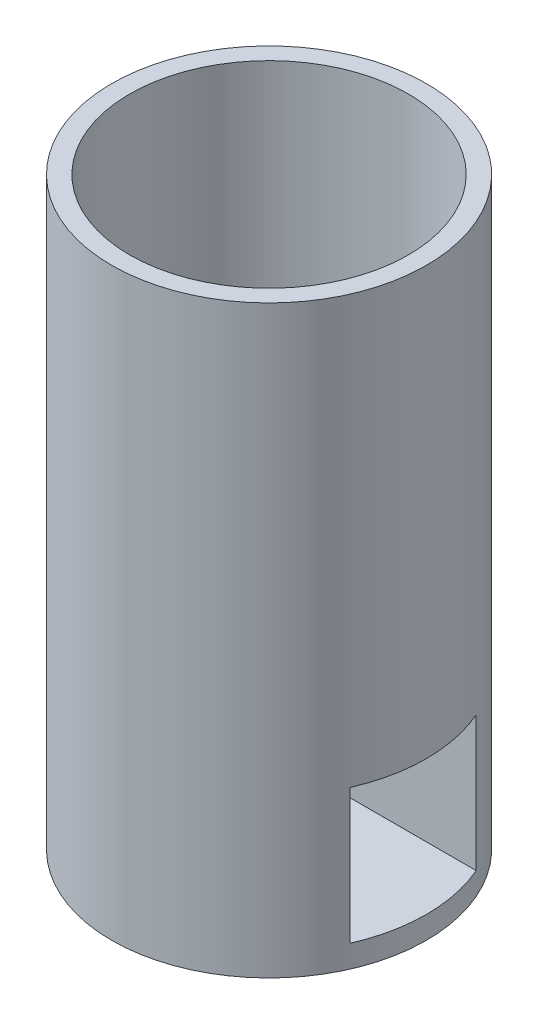
SolidWorks part; units mm, degrees
ref_plane "Front Plane" through (0, 0, 0) normal (0, 0, 1) x (1, 0, 0)
ref_plane "Top Plane" through (0, 0, 0) normal (0, 1, 0) x (1, 0, 0)
ref_plane "Right Plane" through (0, 0, 0) normal (1, 0, 0) x (0, 0, -1)
sketch "Sketch1" plane through (0, 0, 0) normal (0, 1, 0) x (1, 0, 0)
  line L1 (-9.2182, 6.0273) -> (15.7818, 6.0273)
  line L2 (-9.2182, 6.0273) -> (-9.2182, -9.9727)
  line L3 (-9.2182, -9.9727) -> (15.7818, -9.9727)
  line L4 (15.7818, 6.0273) -> (15.7818, -9.9727)
  dimension "D1" = 16
  dimension "D2" = 25
extrude "Boss-Extrude1" add sketch "Sketch1" along normal blind 20
sketch "Sketch6" plane through (0, 0, 0) normal (0, 1, 0) x (1, 0, 0)
  circle A0 centre (3.8725, -1.9531) radius 17.5
extrude "Boss-Extrude4" add sketch "Sketch6" along normal blind 65
sketch "Sketch2" plane through (-9.2182, 0, 0) normal (-1, 0, 0) x (0, 0, 1)
  line L1 (-5.0273, 17.5) -> (8.9727, 17.5)
  line L2 (-5.0273, 17.5) -> (-5.0273, 2.5)
  line L3 (-5.0273, 2.5) -> (8.9727, 2.5)
  line L4 (8.9727, 17.5) -> (8.9727, 2.5)
  line L7 (-15.5469, 0) -> (19.4531, 0) construction
  dimension "D1" = 2.5
  dimension "D4" = 15
extrude "Cut-Extrude1" cut sketch "Sketch2" against normal blind 40 and the other way blind 65
sketch "Sketch3" plane through (0, 0, 0) normal (0, -1, 0) x (-1, 0, 0)
  line L3 (12.1579, -8.9727) -> (-19.903, -8.9727) construction
  circle A0 centre (-9.7818, -1.9727) radius 1.05
  circle A1 centre (0.2182, -1.9727) radius 1.05
  dimension "D6" = 2.1
  dimension "D7" = 2.1
  dimension "D2" = 7
  dimension "D1" = 10
  dimension "D3" = 7
extrude "Cut-Extrude2" cut sketch "Sketch3" against normal blind 10
sketch "Sketch7" plane through (0, 65, 0) normal (0, 1, 0) x (1, 0, 0)
  circle A0 centre (3.8725, -1.9531) radius 15.5
  circle A1 centre (3.8725, -1.9531) radius 17.5 construction
  dimension "D1" = 0
  dimension "D2" = 2
extrude "Cut-Extrude3" cut sketch "Sketch7" against normal blind 30
